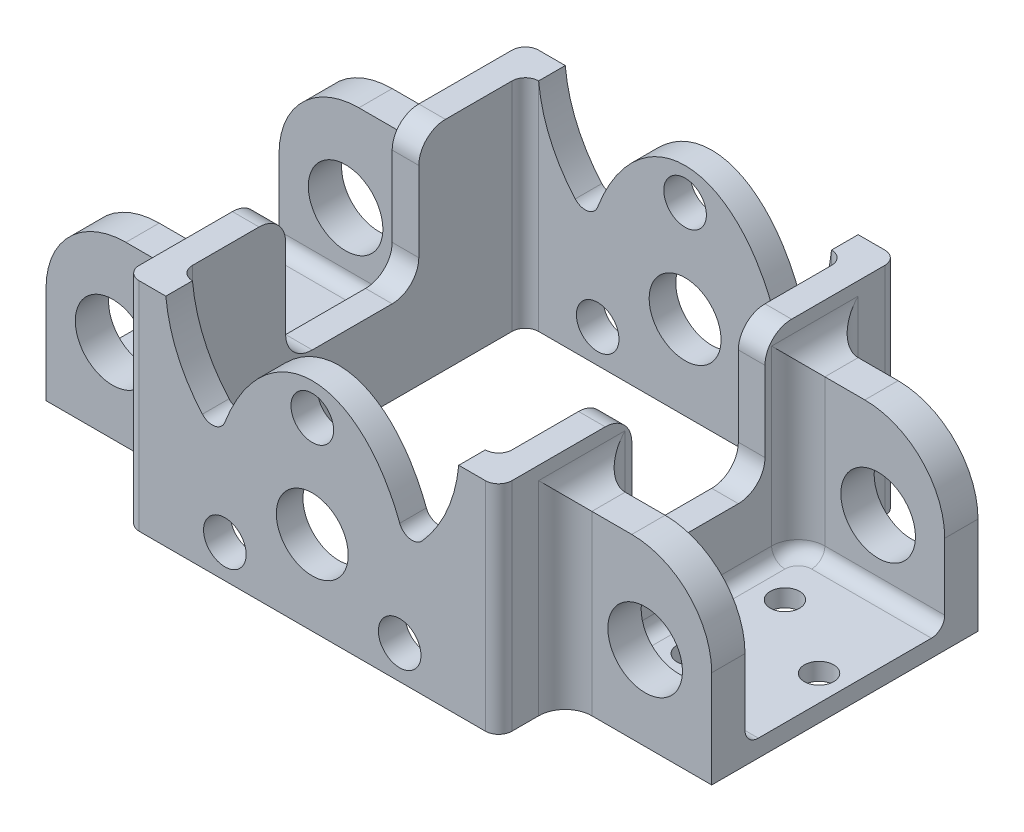
SolidWorks part; units mm, degrees
ref_plane "Front Plane" through (0, 0, 0) normal (0, 0, 1) x (1, 0, 0)
ref_plane "Top Plane" through (0, 0, 0) normal (0, 1, 0) x (1, 0, 0)
ref_plane "Right Plane" through (0, 0, 0) normal (1, 0, 0) x (0, 0, -1)
sketch "Sketch1" plane through (0, 0, 0) normal (0, 0, 1) x (1, 0, 0)
  line L0 (-20.32, 22.3266) -> (-20.32, 12.7) construction
  line L1 (-34.3803, 25.4) -> (-62.23, 25.4) construction
  line L2 (-52.07, 25.4) -> (11.43, 25.4)
  line L3 (-52.07, 25.4) -> (-52.07, 3.81)
  line L4 (-52.07, 3.81) -> (11.43, 3.81)
  line L5 (11.43, 25.4) -> (11.43, 3.81)
  circle A0 centre (-20.32, 12.7) radius 3.429 construction
  circle A1 centre (-11.9831, 7.8867) radius 2.032 construction
  circle A2 centre (-28.6569, 7.8867) radius 2.032 construction
  circle A3 centre (-20.32, 22.3266) radius 2.032 construction
  circle A4 centre (-20.32, 12.7) radius 3.429
  circle A5 centre (-11.9831, 7.8867) radius 2.032
  circle A6 centre (-28.6569, 7.8867) radius 2.032
  circle A7 centre (-20.32, 22.3266) radius 2.032
  circle A8 centre (-45.72, 12.7) radius 3.556 construction
  circle A9 centre (-45.72, 12.7) radius 3.556
  circle A10 centre (5.08, 12.7) radius 3.556
  dimension "D1" = 31.75
  dimension "D2" = 31.75
  dimension "D3" = 21.59
extrude "Boss-Extrude1" add sketch "Sketch1" along normal blind 38.1
sketch "Sketch2" plane through (0, 25.4, 0) normal (0, 1, 0) x (1, 0, 0)
  line L0 (-20.32, 0) -> (-20.32, -38.1) construction
  line L1 (11.43, 0) -> (-52.07, 0) construction
  line L2 (11.43, -38.1) -> (-52.07, -38.1) construction
  line L3 (-38.1, 0) -> (-38.1, -6.35)
  line L4 (-35.56, -2.54) -> (-5.08, -2.54)
  line L5 (-35.56, -2.54) -> (-35.56, -35.56)
  line L6 (-35.56, -35.56) -> (-5.08, -35.56)
  line L7 (-5.08, -2.54) -> (-5.08, -35.56)
  line L8 (-38.1, -6.35) -> (-52.07, -6.35)
  line L9 (-52.07, -38.1) -> (-52.07, 0) construction
  line L10 (-52.07, -9.525) -> (-52.07, -28.575)
  line L11 (-52.07, -9.525) -> (-38.1, -9.525)
  line L12 (-38.1, -9.525) -> (-38.1, -28.575)
  line L13 (-38.1, -28.575) -> (-52.07, -28.575)
  line L14 (-52.07, -28.575) -> (-52.07, -31.75)
  line L15 (-52.07, -31.75) -> (-38.1, -31.75)
  line L16 (-38.1, -31.75) -> (-38.1, -38.1)
  line L17 (-52.07, -6.35) -> (-52.07, 0)
  line L18 (-52.07, 0) -> (-38.1, 0)
  line L19 (-52.07, -31.75) -> (-52.07, -38.1)
  line L20 (-52.07, -38.1) -> (-38.1, -38.1)
  line L21 (11.43, -38.1) -> (-2.54, -38.1)
  line L22 (11.43, -31.75) -> (11.43, -38.1)
  line L23 (11.43, 0) -> (-2.54, 0)
  line L24 (11.43, -6.35) -> (11.43, 0)
  line L25 (-2.54, -31.75) -> (-2.54, -38.1)
  line L26 (11.43, -31.75) -> (-2.54, -31.75)
  line L27 (11.43, -28.575) -> (11.43, -31.75)
  line L28 (-2.54, -28.575) -> (11.43, -28.575)
  line L29 (-2.54, -9.525) -> (-2.54, -28.575)
  line L30 (11.43, -9.525) -> (-2.54, -9.525)
  line L31 (11.43, -9.525) -> (11.43, -28.575)
  line L32 (-2.54, -6.35) -> (11.43, -6.35)
  line L33 (-2.54, 0) -> (-2.54, -6.35)
  line M1 (11.43, 0) -> (-52.07, 0)
  line M2 (-52.07, 0) -> (-52.07, -38.1)
  line M3 (-52.07, -38.1) -> (11.43, -38.1)
  line M4 (11.43, -38.1) -> (11.43, 0)
  dimension "D1" = 30.48
  dimension "D2" = 15.24
  dimension "D3" = 2.54
  dimension "D4" = 2.54
  dimension "D5" = 2.54
  dimension "D6" = 6.35
  dimension "D7" = 3.175
  dimension "D8" = 3.175
  dimension "D9" = 6.35
extrude "Cut-Extrude1" cut sketch "Sketch2" against normal through all contours L13 L12 L11 M2 | L8 L3 M1 M2 | L16 L15 M2 M3 | L4 L0 L6 L7 | L0 L4 L5 L6 | L30 L29 L28 M4 | L26 L25 M4 M3 | L33 L32 M1 M4 region at (-12.7, 25.4, 19.05) region at (-27.94, 25.4, 19.05) region at (4.445, 25.4, 3.175) region at (-45.085, 25.4, 3.175) region at (-45.085, 25.4, 34.925) region at (4.445, 25.4, 34.925) region at (4.445, 25.4, 19.05) region at (-45.085, 25.4, 19.05)
fillet "Fillet1" radius 2.54 8 edges at (-2.54, 14.605, 28.575) (-2.54, 14.605, 31.75) (-2.54, 14.605, 9.525) (-2.54, 14.605, 6.35) (-38.1, 14.605, 31.75) (-38.1, 14.605, 28.575) (-38.1, 14.605, 6.35) (-38.1, 14.605, 9.525)
fillet "Fillet2" radius 1.27 4 edges at (-35.56, 14.605, 35.56) (-35.56, 14.605, 2.54) (-5.08, 14.605, 35.56) (-5.08, 14.605, 2.54)
fillet "Fillet3" radius 1.27 4 edges at (-2.54, 14.605, 38.1) (-38.1, 14.605, 38.1) (-38.1, 14.605, 0) (-2.54, 14.605, 0)
sketch "Sketch3" plane through (0, 0, 38.1) normal (0, 0, 1) x (1, 0, 0)
  line L0 (-52.07, 21.59) -> (-38.1, 21.59)
  line L1 (-52.07, 3.81) -> (-52.07, 25.4) construction
  line L2 (-38.1, 3.81) -> (-38.1, 25.4) construction
  line L3 (-2.54, 21.59) -> (11.43, 21.59)
  line L4 (-2.54, 25.4) -> (-2.54, 3.81) construction
  line L5 (11.43, 3.81) -> (11.43, 25.4) construction
  line L6 (-52.07, 3.81) -> (-40.64, 3.81) construction
  line L7 (-45.72, 21.59) -> (-45.72, 3.81) construction
  line L8 (-52.07, 21.59) -> (-52.07, 25.4)
  line L9 (-52.07, 25.4) -> (-38.1, 25.4)
  line L10 (-38.1, 25.4) -> (-38.1, 21.59)
  line L11 (-2.54, 21.59) -> (-2.54, 25.4)
  line L12 (-2.54, 25.4) -> (11.43, 25.4)
  line L13 (11.43, 25.4) -> (11.43, 21.59)
  point P16 (-45.72, 12.7)
extrude "Cut-Extrude2" cut sketch "Sketch3" against normal through all
fillet "Fillet4" radius 2.54 4 edges at (-2.54, 21.59, 30.1625) (-2.54, 21.59, 7.9375) (-38.1, 21.59, 30.1625) (-38.1, 21.59, 7.9375)
sketch "Sketch4" plane through (-38.1, 0, 0) normal (-1, 0, 0) x (0, 0, 1)
  line L0 (1.27, 25.4) -> (36.83, 25.4) construction
  line L1 (12.7, 25.4) -> (25.4, 25.4)
  line L2 (12.7, 25.4) -> (12.7, 12.7)
  line L3 (12.7, 12.7) -> (25.4, 12.7)
  line L4 (25.4, 25.4) -> (25.4, 12.7)
  line L7 (19.05, 25.4) -> (19.05, 12.7) construction
  dimension "D1" = 12.7
  dimension "D3" = 12.7
extrude "Cut-Extrude3" cut sketch "Sketch4" against normal through all
sketch "Sketch5" plane through (0, 3.81, 0) normal (0, -1, 0) x (1, 0, 0)
  line L0 (11.43, 28.575) -> (11.43, 9.525)
  line L1 (-52.07, 28.575) -> (-52.07, 9.525)
  line L2 (-52.07, 9.525) -> (-40.64, 9.525) construction
  line L3 (-38.1, 12.065) -> (-38.1, 26.035) construction
  line L4 (-40.64, 28.575) -> (-52.07, 28.575) construction
  line L5 (0, 28.575) -> (11.43, 28.575) construction
  line L6 (-2.54, 12.065) -> (-2.54, 26.035) construction
  line L7 (11.43, 9.525) -> (0, 9.525) construction
  line L8 (-52.07, 9.525) -> (-40.64, 9.525)
  line L9 (-38.1, 12.065) -> (-38.1, 26.035)
  line L10 (-40.64, 28.575) -> (-52.07, 28.575)
  line L11 (0, 28.575) -> (11.43, 28.575)
  line L12 (-2.54, 12.065) -> (-2.54, 26.035)
  line L13 (11.43, 9.525) -> (0, 9.525)
  line L14 (-41.91, 23.495) -> (-41.91, 14.605) construction
  line L15 (-41.91, 23.495) -> (-49.609, 19.05) construction
  line L16 (-49.609, 19.05) -> (-41.91, 14.605) construction
  line L17 (-41.91, 19.05) -> (-38.1, 19.05) construction
  line L18 (-20.32, 35.56) -> (-20.32, 2.54) construction
  line L19 (-34.29, 35.56) -> (-6.35, 35.56) construction
  line L20 (-34.29, 2.54) -> (-6.35, 2.54) construction
  line L21 (1.27, 19.05) -> (-2.54, 19.05) construction
  line L22 (8.969, 19.05) -> (1.27, 14.605) construction
  line L23 (1.27, 23.495) -> (8.969, 19.05) construction
  line L24 (1.27, 23.495) -> (1.27, 14.605) construction
  arc A0 (-40.64, 9.525) -> (-38.1, 12.065) centre (-40.64, 12.065) ccw construction
  arc A1 (-38.1, 26.035) -> (-40.64, 28.575) centre (-40.64, 26.035) ccw construction
  arc A2 (0, 28.575) -> (-2.54, 26.035) centre (0, 26.035) ccw construction
  arc A3 (-2.54, 12.065) -> (0, 9.525) centre (0, 12.065) ccw construction
  arc A4 (-40.64, 9.525) -> (-38.1, 12.065) centre (-40.64, 12.065) ccw
  arc A5 (-38.1, 26.035) -> (-40.64, 28.575) centre (-40.64, 26.035) ccw
  arc A6 (0, 28.575) -> (-2.54, 26.035) centre (0, 26.035) ccw
  arc A7 (-2.54, 12.065) -> (0, 9.525) centre (0, 12.065) ccw
  circle A8 centre (-41.91, 23.495) radius 1.397
  circle A9 centre (-41.91, 14.605) radius 1.397
  circle A10 centre (-49.609, 19.05) radius 1.397
  circle A11 centre (8.969, 19.05) radius 1.397
  circle A12 centre (1.27, 14.605) radius 1.397
  circle A13 centre (1.27, 23.495) radius 1.397
  dimension "D1" = 2.794
  dimension "D2" = 8.89
  dimension "D3" = 3.81
extrude "Boss-Extrude2" add sketch "Sketch5" against normal blind 2.54
fillet "Fillet5" radius 1.27 10 edges at (5.715, 6.35, 28.575) (5.715, 6.35, 9.525) (-1.7961, 6.35, 10.2689) (-2.54, 6.35, 19.05) (-46.355, 6.35, 9.525) (-38.8439, 6.35, 10.2689) (-38.1, 6.35, 19.05) (-38.8439, 6.35, 27.8311) (-1.7961, 6.35, 27.8311) (-46.355, 6.35, 28.575)
fillet "Fillet6" radius 7.62 4 edges at (11.43, 21.59, 7.9375) (11.43, 21.59, 30.1625) (-52.07, 21.59, 7.9375) (-52.07, 21.59, 30.1625)
fillet "Fillet7" radius 2.54 4 edges at (-36.83, 25.4, 12.7) (-3.81, 25.4, 12.7) (-3.81, 25.4, 25.4) (-36.83, 25.4, 25.4)
fillet "Fillet8" radius 2.54 4 edges at (-36.83, 12.7, 25.4) (-36.83, 12.7, 12.7) (-3.81, 12.7, 12.7) (-3.81, 12.7, 25.4)
sketch "Sketch6" plane through (-52.07, 0, 0) normal (-1, 0, 0) x (0, 0, 1)
  line L0 (38.1, 25.4) -> (38.1, 3.81) construction
  line L1 (0, 3.81) -> (38.1, 3.81)
  line L2 (0, 3.81) -> (0, 4.699)
  line L3 (0, 4.699) -> (38.1, 4.699)
  line L4 (38.1, 3.81) -> (38.1, 4.699)
  dimension "D1" = 0.889
extrude "Cut-Extrude4" cut sketch "Sketch6" against normal through all
sketch "Sketch7" plane through (0, 0, 0) normal (0, 0, -1) x (-1, 0, 0)
  line L1 (3.81, 25.4) -> (36.83, 25.4) construction
  circle A0 centre (20.32, 26.7335) radius 14.0335
  circle A1 centre (20.32, 12.7) radius 3.429 construction
  circle A2 centre (11.9831, 7.8867) radius 2.032 construction
  circle A3 centre (28.6569, 7.8867) radius 2.032 construction
  ellipse E0 centre (20.32, 9.271) end of major axis (20.32, -6.858) minor radius 9.8244
  line M8 (36.83, 25.4) -> (3.81, 25.4)
extrude "Cut-Extrude5" cut sketch "Sketch7" against normal through all contours E0 A0 M8 | E0 A0 M8 region at (-11.1481, 22.2324, 0) region at (-29.4919, 22.2324, 0)
fillet "Fillet9" radius 1.27 4 edges at (-29.2696, 15.9241, 1.27) (-11.3704, 15.9241, 1.27) (-29.2696, 15.9241, 36.83) (-11.3704, 15.9241, 36.83)
